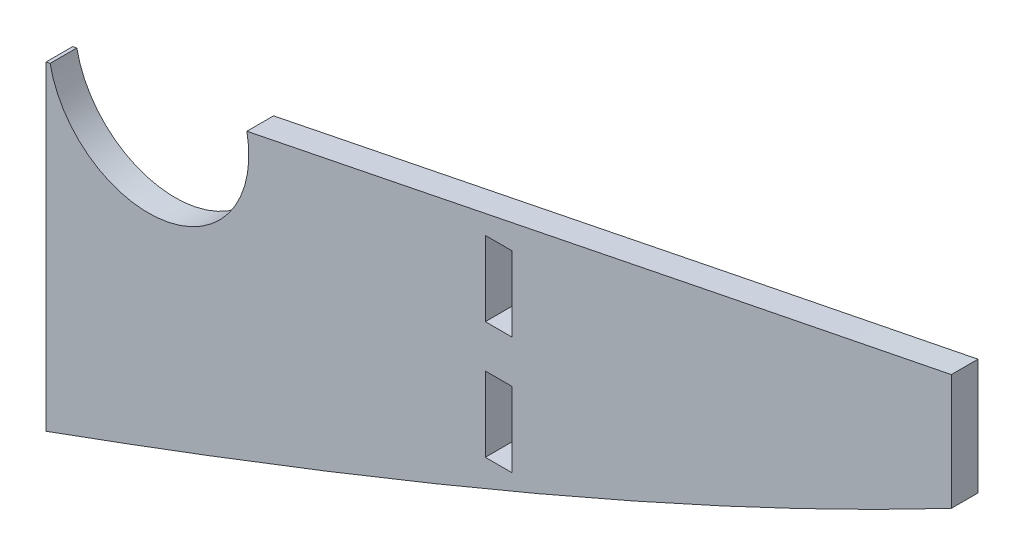
SolidWorks part; units mm, degrees
material "Balsa"
ref_plane "Front Plane" through (0, 0, 0) normal (0, 0, 1) x (1, 0, 0)
ref_plane "Top Plane" through (0, 0, 0) normal (0, 1, 0) x (1, 0, 0)
ref_plane "Right Plane" through (0, 0, 0) normal (1, 0, 0) x (0, 0, -1)
ref_plane "Plane2" through (0, 0, -652.5715) normal (0, 0, 1) x (1, 0, 0)
sketch "Sketch3" plane through (0, 0, -652.5715) normal (0, 0, 1) x (1, 0, 0)
  line L0 (266.9765, 14.3317) -> (266.7, 14.2761)
  line L4 (267.1904, 14.3747) -> (266.7, 14.2761)
  line L5 (374.396, 22.1319) -> (374.396, 35.9161)
  line L6 (266.7, -23.7693) -> (266.7, 14.2761)
  circle A0 centre (278.892, 16.7387) radius 11.938
  arc A2 (267.1904, 14.3747) -> (290.5967, 19.0875) centre (278.892, 16.7387) ccw
  spline S0 degree 3 poles (-349.4773, -1785.3794) (-543.6607, -114.5151) (-88.3164, -161.3774) (303.2447, -9.9898) (312.3076, -6.3596) (330.3153, 1.1877) (339.2629, 5.106) (590.5882, 121.5285) (766.5692, 372.5867) (292.9604, 1979.1371) knots -10.248178 -10.248178 -10.248178 -10.248178 0.25 0.25 0.5 0.5 0.75 0.75 7.594048 7.594048 7.594048 7.594048 only from (266.7, -23.7693) to (374.396, 22.1319)
  spline S1 degree 3 poles (266.7, -23.7693) (275.8805, -20.4431) (285.0295, -17.0322) (303.2447, -9.9898) (312.3076, -6.3596) (330.3153, 1.1877) (339.2629, 5.106) (356.9768, 13.3116) (365.7449, 17.5996) (374.396, 22.1319) knots 0 0 0 0 0.25 0.25 0.5 0.5 0.75 0.75 1 1 1 1
  spline S2 degree 3 poles (2008.4638, -902.6808) (1288.2411, 213.3598) (809.6279, 123.5679) (-258.7727, -91.4789) (-847.3866, -222.5745) (-1592.5008, 425.9809) knots -16.503098 -16.503098 -16.503098 -16.503098 0.5 0.5 21.55285 21.55285 21.55285 21.55285 only from (374.396, 35.9161) to (290.1652, 19.0006)
  spline S3 degree 3 poles (374.396, 35.9161) (360.3505, 33.1321) (346.3121, 30.3121) (318.3815, 24.6902) (304.4894, 21.8871) (290.5967, 19.0875) knots 0 0 0 0 0.5 0.5 0.994877 0.994877 0.994877 0.994877
extrude "Boss-Extrude1" add sketch "Sketch3" along normal blind 3.175 contours L5 S3 A2 L4 L6 S1 region at (315.4071, 8.7665, -652.5715)
sketch "Sketch7" plane through (0, 0, -649.3965) normal (0, 0, 1) x (1, 0, 0)
  line L0 (266.7, 11.1097) -> (374.396, 11.1097) construction
  line L1 (318.9605, 22.5397) -> (322.1355, 22.5397)
  line L2 (318.9605, 22.5397) -> (318.9605, 13.6497)
  line L3 (318.9605, 13.6497) -> (322.1355, 13.6497)
  line L4 (322.1355, 22.5397) -> (322.1355, 13.6497)
  line L5 (318.9605, 8.5697) -> (322.1355, 8.5697)
  line L6 (318.9605, 8.5697) -> (318.9605, -0.3203)
  line L7 (318.9605, -0.3203) -> (322.1355, -0.3203)
  line L8 (322.1355, 8.5697) -> (322.1355, -0.3203)
  line L9 (374.396, 11.1097) -> (374.396, 22.1319) construction
  line L10 (266.7, -23.7693) -> (266.7, 14.2761) construction
  line L11 (320.548, -2.9056) -> (320.548, 25.1249) construction
  line L14 (374.396, 22.1319) -> (374.396, 35.9161)
  line L16 (267.1904, 14.3747) -> (266.7, 14.2761)
  line L17 (266.7, 14.2761) -> (266.7, -23.7693)
  line L18 (374.396, 22.1319) -> (374.396, 35.9161) construction
  line L20 (266.7, 14.2761) -> (266.7, -23.7693) construction
  arc A1 (267.1904, 14.3747) -> (290.5967, 19.0875) centre (278.892, 16.7387) ccw
  spline S1 degree 3 poles (374.396, 35.9161) (360.3505, 33.1321) (346.3121, 30.3121) (318.3815, 24.6902) (304.4894, 21.8871) (290.5967, 19.0875) knots 0 0 0 0 0.5 0.5 0.994877 0.994877 0.994877 0.994877 construction
  spline S2 degree 3 poles (266.7, -23.7693) (275.8805, -20.4431) (285.0295, -17.0322) (303.2447, -9.9898) (312.3076, -6.3596) (330.3153, 1.1877) (339.2629, 5.106) (356.9768, 13.3116) (365.7449, 17.5996) (374.396, 22.1319) knots 0 0 0 0 0.25 0.25 0.5 0.5 0.75 0.75 1 1 1 1 construction
  spline S3 degree 3 poles (2496.0404, -1775.7133) (1489.1782, 250.7699) (909.8042, 143.7313) (-424.2192, -124.7798) (-1176.7262, -296.9177) (-2258.4933, 1171.2494) knots -20.071334 -20.071334 -20.071334 -20.071334 0.5 0.5 27.445978 27.445978 27.445978 27.445978 only from (374.396, 35.9161) to (290.5967, 19.0875)
  spline S5 degree 3 poles (-194.8193, -2773.3129) (-697.5352, -93.4736) (-152.0866, -186.0327) (303.2447, -9.9898) (312.3076, -6.3596) (330.3153, 1.1877) (339.2629, 5.106) (632.183, 140.7966) (824.9907, 462.8063) (-11.0717, 2931.7486) knots -11.998641 -11.998641 -11.998641 -11.998641 0.25 0.25 0.5 0.5 0.75 0.75 8.768127 8.768127 8.768127 8.768127 only from (266.7, -23.7693) to (374.396, 22.1319)
  spline S6 degree 3 poles (374.396, 35.9161) (360.3505, 33.1318) (346.3122, 30.3117) (310.416, 23.086) (288.5604, 18.6693) (266.7, 14.2761) knots 0 0 0 0 0.5 0.5 1.27861 1.27861 1.27861 1.27861 construction
  spline S7 degree 3 poles (266.7, -23.7693) (275.8805, -20.4431) (285.0295, -17.0322) (303.2447, -9.9898) (312.3076, -6.3596) (330.3153, 1.1877) (339.2629, 5.106) (356.9768, 13.3116) (365.7449, 17.5996) (374.396, 22.1319) knots 0 0 0 0 0.25 0.25 0.5 0.5 0.75 0.75 1 1 1 1 construction
  point P18 (320.548, 11.1097)
  point P26 (320.548, 13.6497)
  dimension "D1" = 3.175
  dimension "D2" = 8.89
  dimension "D3" = 2.54
  dimension "D4" = 2.54
  dimension "D5" = 0
extrude "Cut-Extrude1" cut sketch "Sketch7" against normal through all
